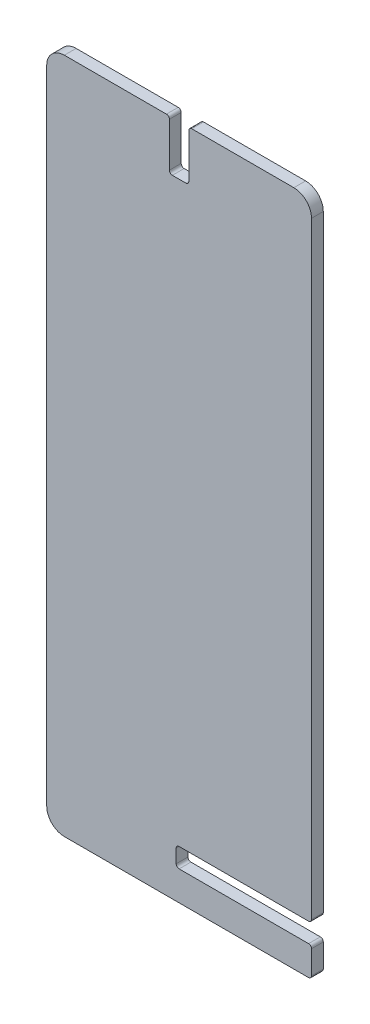
SolidWorks part; units mm, degrees
ref_plane "Alzado" through (0, 0, 0) normal (0, 0, 1) x (1, 0, 0)
ref_plane "Planta" through (0, 0, 0) normal (0, 1, 0) x (1, 0, 0)
ref_plane "Vista lateral" through (0, 0, 0) normal (1, 0, 0) x (0, 0, -1)
sketch "Croquis1" plane through (0, 0, 0) normal (0, 0, 1) x (1, 0, 0)
  line L1 (-22.5, 45) -> (22.5, 45)
  line L2 (-22.5, 45) -> (-22.5, -70)
  line L3 (-22.5, -70) -> (22.5, -70)
  line L4 (22.5, 45) -> (22.5, -70)
  dimension "D1" = 45
  dimension "D2" = 22.5
  dimension "D3" = 115
  dimension "D4" = 45
extrude "Saliente-Extruir1" add sketch "Croquis1" along normal blind 2 contours L2 L3 L4 L1
sketch "Croquis3" plane through (0, 0, 2) normal (0, 0, 1) x (1, 0, 0)
  line L0 (22.5, 45) -> (22.5, -70) construction
  line L1 (22.5, -61.7) -> (-0.5, -61.7)
  line L2 (22.5, -61.7) -> (22.5, -65)
  line L3 (22.5, -65) -> (-0.5, -65)
  line L4 (-0.5, -61.7) -> (-0.5, -65)
  line L5 (-22.5, -70) -> (22.5, -70) construction
  dimension "D1" = 3.3
  dimension "D2" = 5
  dimension "D3" = 23
extrude "Cortar-Extruir2" cut sketch "Croquis3" against normal up to surface (2 mm away) up to face at (0, -12.5, 0)
fillet "Redondeo1" radius 3 3 edges at (-22.5, -70, 1) (22.5, 45, 1) (-22.5, 45, 1)
sketch "Croquis4" plane through (0, 0, 2) normal (0, 0, 1) x (1, 0, 0)
  line L5 (0, 0) -> (0, 53.685) construction
  line L6 (-19.5, 45) -> (19.5, 45) construction
  line L7 (-1.65, 45) -> (1.65, 45)
  line L8 (-1.65, 45) -> (-1.65, 36.5)
  line L9 (-1.65, 36.5) -> (1.65, 36.5)
  line L10 (1.65, 45) -> (1.65, 36.5)
  point P9 (0, 36.5)
  dimension "D2" = 1.65
  dimension "D3" = 8.5
extrude "Cortar-Extruir3" cut sketch "Croquis4" against normal up to surface (2 mm away) up to face at (2.1708, -25.9799, 0)
fillet "Redondeo2" radius 0.5 9 edges at (-0.5, -61.7, 1) (-0.5, -65, 1) (22.5, -70, 1) (22.5, -65, 1) (22.5, -61.7, 1) (-1.65, 36.5, 1) (1.65, 36.5, 1) (-1.65, 45, 1) (1.65, 45, 1)
